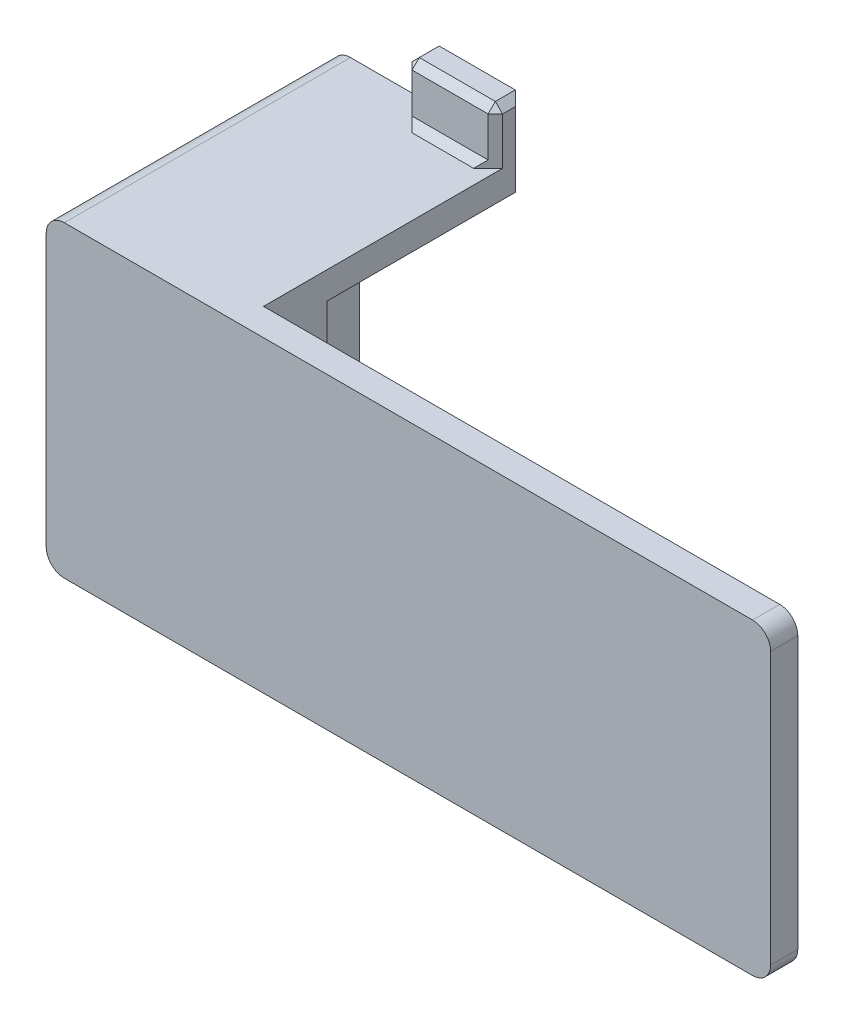
SolidWorks part; units mm, degrees
ref_plane "Front Plane" through (0, 0, 0) normal (0, 0, 1) x (1, 0, 0)
ref_plane "Top Plane" through (0, 0, 0) normal (0, 1, 0) x (1, 0, 0)
ref_plane "Right Plane" through (0, 0, 0) normal (1, 0, 0) x (0, 0, -1)
sketch "Sketch1" plane through (0, 0, 0) normal (0, 1, 0) x (1, 0, 0)
  line L0 (-16.51, 0) -> (16.51, 0)
  line L1 (16.51, 0) -> (16.51, 3.81)
  line L2 (16.51, 3.81) -> (-12.7, 3.81)
  line L3 (-12.7, 3.81) -> (-12.7, 31.242)
  line L7 (-16.51, 31.242) -> (-16.51, 0)
  line L8 (10.16, 3.81) -> (10.16, 0)
  line L9 (-12.7, 31.242) -> (-16.51, 31.242)
  point P9 (0, 0)
  dimension "D1" = 31.242
  dimension "D3" = 3.81
  dimension "D5" = 3.81
  dimension "D6" = 33.02
  dimension "D7" = 6.35
extrude "Boss-Extrude1" add sketch "Sketch1" along normal blind 21.59 and the other way blind 21.59 contours L8 L2 L3 L7 L0 region at (-16.0992, 0, -15.621)
extrude "Boss-Extrude2" add sketch "Sketch1<4>" along normal blind 6.35 and the other way blind 6.35 contours L2 L8 L0 L1 region at (13.335, 0, -1.905)
sketch "Sketch1<4>" plane through (0, 0, 0) normal (0, 1, 0) x (1, 0, 0) same geometry as "Sketch1"
sketch "Sketch3" plane through (0, 21.59, 0) normal (0, 1, 0) x (1, 0, 0)
  line L0 (-16.51, 31.242) -> (-16.51, 0) construction
  line L1 (-16.51, 31.242) -> (10.16, 31.242)
  line L2 (-16.51, 31.242) -> (-16.51, 0)
  line L3 (-16.51, 0) -> (10.16, 0)
  line L4 (10.16, 31.242) -> (10.16, 0)
extrude "Boss-Extrude3" add sketch "Sketch3" against normal blind 3.81
mirror "Mirror1" about plane through (0, 0, 0) normal (0, 1, 0) of "Boss-Extrude3"
fillet "Fillet1" radius 2.54 2 edges at (-16.51, -21.59, -15.621) (-16.51, 21.59, -15.621)
chamfer "Chamfer1" distance 1.27 angle 45 5 edges at (16.51, -6.35, -1.905) (13.335, -6.35, -3.81) (16.51, 0, -3.81) (13.335, 6.35, -3.81) (16.51, 6.35, -1.905)
sketch "Sketch9" plane through (0, -21.59, 0) normal (0, -1, 0) x (1, 0, 0)
  line L1 (10.16, -31.242) -> (-2.54, -31.242)
  line L2 (10.16, -31.242) -> (10.16, -27.432)
  line L3 (10.16, -27.432) -> (-2.54, -27.432)
  line L4 (-2.54, -31.242) -> (-2.54, -27.432)
  dimension "D1" = 3.81
  dimension "D2" = 12.7
extrude "Boss-Extrude6" add sketch "Sketch9" along normal blind 7.62
chamfer "Chamfer2" distance 1.016 angle 45 5 edges at (10.16, -29.21, -29.337) (-2.54, -29.21, -29.337) (-2.54, -25.4, -27.432) (10.16, -25.4, -27.432) (3.81, -29.21, -27.432)
chamfer "Chamfer3" distance 1.016 angle 45 2 edges at (3.81, -21.59, -27.432) (10.16, -22.987, -31.242)
mirror "Mirror2" about plane through (0, 0, 0) normal (0, 1, 0) of "Boss-Extrude6", "Chamfer2"
sketch "Sketch10" plane through (0, 0, 0) normal (0, 0, 1) x (1, 0, 0)
  line L0 (10.16, 6.35) -> (10.16, 21.59) construction
  line L1 (10.16, 6.35) -> (15.24, 6.35) construction
  line L2 (16.51, 5.08) -> (15.24, 6.35) construction
  line L3 (16.51, -5.08) -> (16.51, 5.08) construction
  line L4 (15.24, -6.35) -> (16.51, -5.08) construction
  line L5 (10.16, -6.35) -> (15.24, -6.35) construction
  line L6 (10.16, -21.59) -> (10.16, -6.35) construction
  line L7 (-13.97, -21.59) -> (10.16, -21.59) construction
  line L8 (-16.51, -19.05) -> (-16.51, 19.05) construction
  line L9 (-13.97, 21.59) -> (10.16, 21.59) construction
  line L10 (10.16, 6.35) -> (10.16, 21.59)
  line L11 (10.16, 6.35) -> (15.24, 6.35)
  line L12 (16.51, 5.08) -> (15.24, 6.35)
  line L13 (16.51, -5.08) -> (16.51, 5.08)
  line L14 (15.24, -6.35) -> (16.51, -5.08)
  line L15 (10.16, -6.35) -> (15.24, -6.35)
  line L16 (10.16, -21.59) -> (10.16, -6.35)
  line L17 (-13.97, -21.59) -> (10.16, -21.59)
  line L18 (-16.51, -19.05) -> (-16.51, 19.05)
  line L19 (-13.97, 21.59) -> (10.16, 21.59)
  arc A0 (-16.51, -19.05) -> (-13.97, -21.59) centre (-13.97, -19.05) ccw construction
  arc A1 (-13.97, 21.59) -> (-16.51, 19.05) centre (-13.97, 19.05) ccw construction
  arc A2 (-16.51, -19.05) -> (-13.97, -21.59) centre (-13.97, -19.05) ccw
  arc A3 (-13.97, 21.59) -> (-16.51, 19.05) centre (-13.97, 19.05) ccw
extrude "Boss-Extrude7" add sketch "Sketch10" along normal blind 5.08
sketch "Sketch11" plane through (0, 0, 5.08) normal (0, 0, 1) x (1, 0, 0)
  line L0 (10.16, 21.59) -> (-13.97, 21.59) construction
  line L1 (-13.97, 21.59) -> (82.55, 21.59)
  line L2 (-16.51, 19.05) -> (-16.51, -19.05)
  line L3 (-13.97, -21.59) -> (82.55, -21.59)
  line L4 (85.09, 19.05) -> (85.09, -19.05)
  line L5 (-16.51, 19.05) -> (-16.51, -19.05) construction
  line L6 (-13.97, -21.59) -> (10.16, -21.59) construction
  arc A0 (82.55, 21.59) -> (85.09, 19.05) centre (82.55, 19.05) cw
  arc A1 (82.55, -21.59) -> (85.09, -19.05) centre (82.55, -19.05) ccw
  arc A2 (-16.51, -19.05) -> (-13.97, -21.59) centre (-13.97, -19.05) ccw
  arc A3 (-13.97, 21.59) -> (-16.51, 19.05) centre (-13.97, 19.05) ccw
  dimension "D1" = 2.54
  dimension "D2" = 101.6
extrude "Boss-Extrude8" add sketch "Sketch11" along normal blind 3.81
chamfer "Chamfer4" distance 1.016 angle 45 2 edges at (3.81, 21.59, -27.432) (10.16, 22.987, -31.242)
sketch "Sketch12" plane through (-12.7, 0, 0) normal (1, 0, 0) x (0, 0, -1)
  line L5 (3.81, -17.78) -> (11.43, -17.78)
  line L6 (3.81, -17.78) -> (3.81, -10.16)
  line L7 (3.81, -10.16) -> (11.43, -10.16)
  line L8 (11.43, -17.78) -> (11.43, -10.16)
  dimension "D1" = 7.62
  dimension "D2" = 7.62
extrude "Cut-Extrude2" cut sketch "Sketch12" against normal up to surface (3.81 mm away) up to face at (-16.51, 0, -11.176)
fillet "Fillet8" radius 1.27 6 edges at (-16.51, -13.97, -3.81) (-12.7, -13.97, -11.43) (-16.51, -13.97, -11.43) (-16.51, -17.78, -7.62) (-12.7, -10.16, -7.62) (-16.51, -10.16, -7.62)
